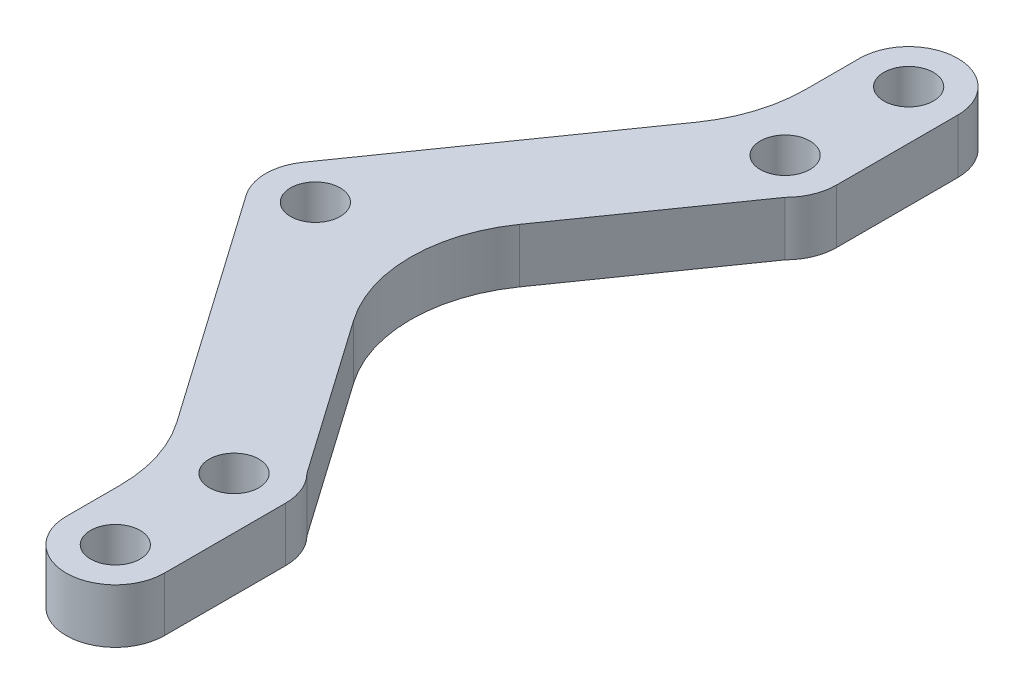
SolidWorks part; units mm, degrees
ref_plane "Front Plane" through (0, 0, 0) normal (0, 0, 1) x (1, 0, 0)
ref_plane "Top Plane" through (0, 0, 0) normal (0, 1, 0) x (1, 0, 0)
ref_plane "Right Plane" through (0, 0, 0) normal (1, 0, 0) x (0, 0, -1)
sketch "Sketch1" plane through (0, 0, 0) normal (0, 1, 0) x (1, 0, 0)
  line L1 (-15.25, -15.25) -> (15.25, -15.25) construction
  line L2 (-15.25, -15.25) -> (-15.25, 15.25) construction
  line L3 (-15.25, 15.25) -> (15.25, 15.25) construction
  line L4 (15.25, -15.25) -> (15.25, 15.25) construction
  line L5 (-15.25, -15.25) -> (15.25, 15.25) construction
  line L6 (-15.25, 15.25) -> (15.25, -15.25) construction
  point P0 (0, 0)
  dimension "D1" = 30.5
sketch "Sketch5" plane through (0, 0, 0) normal (0, 1, 0) x (1, 0, 0)
  line L0 (0, -16) -> (0, 16)
  line L1 (0, 16) -> (-23, 16)
  line L2 (-23, 16) -> (-23, -16)
  line L3 (-23, -16) -> (0, -16)
  line L4 (-11.5, 16) -> (-11.5, -16) construction
  line L5 (-23, 0) -> (0, 0) construction
  point P4 (0, 0)
  point P10 (-15.25, -14.7545)
  dimension "D1" = 23
  dimension "D2" = 32
sketch "Sketch6" plane through (0, 0, 0) normal (0, 1, 0) x (-1, 0, 0)
  line L14 (23, -16) -> (23, 16) construction
  line L20 (23, -16) -> (23, 16) construction
  line L22 (23, 0) -> (0, 0) construction
  circle A2 centre (26, 0) radius 1.375 construction
  dimension "D7" = 3
  dimension "D8" = 2.75
sketch "Sketch2" plane through (0, 0, 0) normal (0, 1, 0) x (1, 0, 0)
  line L0 (-15.25, 15.25) -> (15.25, -15.25) construction
  line L7 (-27.375, 0) -> (-28.75, 0)
  line L8 (-15.25, 15.25) -> (-16.1391, 13.9802) construction
  line L11 (-13.2335, 13.2335) -> (-22.5, 0)
  line L12 (-17.8346, 16.4553) -> (-28.2526, 1.5774)
  line L13 (-12.3982, 15.25) -> (-12.3982, 21.9553)
  line L14 (-17.8346, 16.4553) -> (-17.8346, 21.9553)
  line L15 (-22.5, 0) -> (-24.625, 0)
  line L17 (-12.3982, 21.9553) -> (-17.8346, 21.9553) construction
  arc A0 (-28.2526, 1.5774) -> (-28.75, 0) centre (-26, 0) ccw
  arc A1 (-24.625, 0) -> (-27.375, 0) centre (-26, 0) ccw
  arc A3 (-13.2335, 13.2335) -> (-12.3982, 15.25) centre (-15.25, 15.25) ccw
  arc A4 (-12.3982, 21.9553) -> (-17.8346, 21.9553) centre (-15.1164, 21.9553) ccw
  dimension "D4" = 5.5
  dimension "D5" = 2.75
  dimension "D1" = 3.5
  dimension "D3" = 5.5
extrude "Boss-Extrude1" add sketch "Sketch2" along normal blind 3
sketch "Sketch3" plane through (0, 3, 0) normal (0, 1, 0) x (1, 0, 0)
  circle A0 centre (-15.25, 15.25) radius 1.375
  arc A1 (-24.625, 0) -> (-27.375, 0) centre (-26, 0) ccw construction
  circle A2 centre (-15.1164, 21.9553) radius 1.375
extrude "Cut-Extrude1" cut sketch "Sketch3" against normal through all
mirror "Mirror2" about plane through (-22.5, 3, 0) normal (0, 0, -1) of "Cut-Extrude1", "Boss-Extrude1"
fillet "Fillet1" radius 8 3 edges at (-22.5, 1.5, 0) (-17.8346, 1.5, 16.4553) (-17.8346, 1.5, -16.4553)
